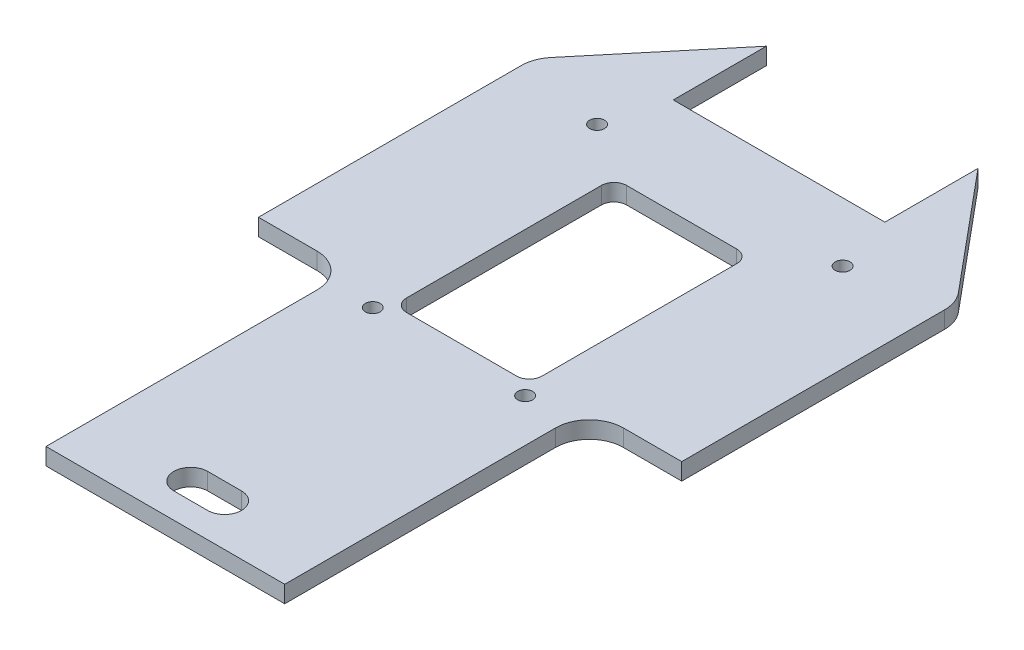
SolidWorks part; units mm, degrees
ref_plane "Front Plane" through (0, 0, 0) normal (0, 0, 1) x (1, 0, 0)
ref_plane "Top Plane" through (0, 0, 0) normal (0, 1, 0) x (1, 0, 0)
ref_plane "Right Plane" through (0, 0, 0) normal (1, 0, 0) x (0, 0, -1)
sketch "Sketch1" plane through (0, 0, 0) normal (0, 1, 0) x (1, 0, 0)
  line L0 (-28.2, -67) -> (28.2, -67)
  line L1 (28.2, -67) -> (28.2, -3)
  line L2 (36.2, 5) -> (50, 5)
  line L3 (50, 5) -> (50, 67.1036)
  line L4 (48.1458, 72.2251) -> (25, 100)
  line L5 (25, 100) -> (25, 78)
  line L6 (25, 78) -> (-25, 78)
  line L7 (-25, 78) -> (-25, 100)
  line L8 (-25, 100) -> (-48.1458, 72.2251)
  line L9 (-50, 67.1036) -> (-50, 5)
  line L10 (-50, 5) -> (-36.2, 5)
  line L11 (-28.2, -3) -> (-28.2, -67)
  line L12 (0, -301.7456) -> (0, 401.93) construction
  line L13 (-50, 70) -> (50, 70) construction
  line L14 (126.3715, 0) -> (-162.7022, 0) construction
  line L15 (132.1823, 64) -> (-95.3575, 64) construction
  line L16 (-13, 3) -> (13, 3)
  line L17 (-16, 6) -> (-16, 52)
  line L18 (-13, 55) -> (13, 55)
  line L19 (16, 6) -> (16, 52)
  line L20 (-16, 3) -> (16, 55) construction
  line L21 (-16, 55) -> (16, 3) construction
  line L22 (-4, -57) -> (4, -57) construction
  line L23 (-4, -53) -> (4, -53)
  line L24 (-4, -61) -> (4, -61)
  circle A0 centre (18, 0) radius 1.75
  circle A1 centre (-18, 0) radius 1.75
  circle A2 centre (29, 64) radius 1.75
  circle A3 centre (-29, 64) radius 1.75
  arc A4 (-13, 3) -> (-16, 6) centre (-13, 6) cw
  arc A5 (13, 3) -> (16, 6) centre (13, 6) ccw
  arc A6 (13, 55) -> (16, 52) centre (13, 52) cw
  arc A7 (-16, 52) -> (-13, 55) centre (-13, 52) cw
  arc A8 (50, 67.1036) -> (48.1458, 72.2251) centre (42, 67.1036) ccw
  arc A9 (-48.1458, 72.2251) -> (-50, 67.1036) centre (-42, 67.1036) ccw
  arc A10 (28.2, -3) -> (36.2, 5) centre (36.2, -3) cw
  arc A11 (-36.2, 5) -> (-28.2, -3) centre (-36.2, -3) cw
  arc A12 (-4, -53) -> (-4, -61) centre (-4, -57) ccw
  arc A13 (4, -61) -> (4, -53) centre (4, -57) ccw
  point P15 (0, 29)
  point P32 (0, -57)
  point P54 (28.2, 5)
  point P62 (0, 0)
  dimension "D13" = 18
  dimension "D15" = 3.5
  dimension "D16" = 3
  dimension "D17" = 8
  dimension "D18" = 8
  dimension "D1" = 56.4
  dimension "D2" = 72
  dimension "D3" = 100
  dimension "D4" = 67
  dimension "D5" = 137
  dimension "D6" = 50
  dimension "D7" = 30
  dimension "D8" = 22
  dimension "D9" = 32
  dimension "D10" = 50
  dimension "D11" = 2
  dimension "D12" = 64
  dimension "D14" = 29
  dimension "D19" = 10
  dimension "D20" = 8
  dimension "D21" = 8
extrude "Boss-Extrude1" add sketch "Sketch1" along normal blind 4
